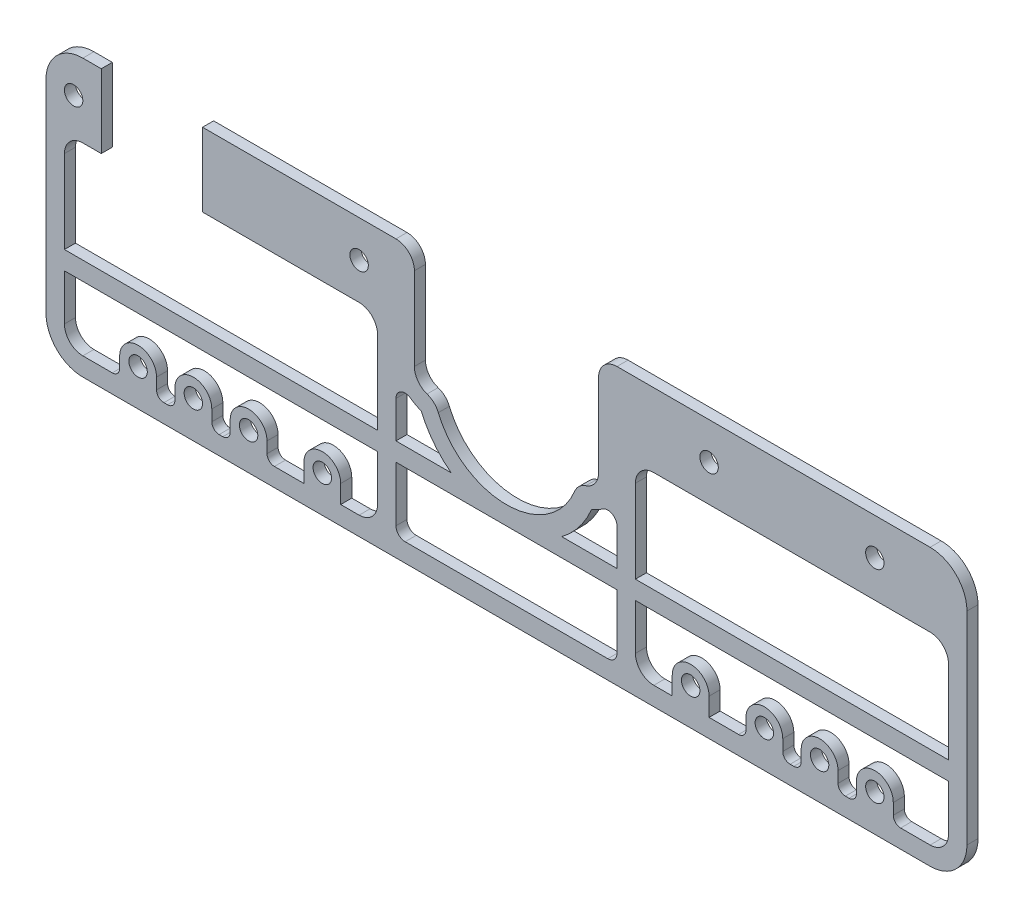
SolidWorks part; units mm, degrees
ref_plane "Front Plane" through (0, 0, 0) normal (0, 0, 1) x (1, 0, 0)
ref_plane "Top Plane" through (0, 0, 0) normal (0, 1, 0) x (1, 0, 0)
ref_plane "Right Plane" through (0, 0, 0) normal (1, 0, 0) x (0, 0, -1)
sketch "Sketch1" plane through (0, 0, 0) normal (0, 0, 1) x (1, 0, 0)
  line L0 (-40, 20) -> (-40, 55) construction
  line L4 (-250, -55) -> (-250, 3.1783)
  line L8 (-50, 75) -> (-230, 75) construction
  line L17 (0, -20) -> (0, -40)
  line L25 (0, -65) -> (0, -75)
  line L26 (0, 75) -> (0, -75) construction
  line L27 (-50, 95) -> (50, 95) construction
  line L34 (0, -75) -> (-230, -75)
  line L156 (-50, 75) -> (-230, 75) construction
  line L161 (0, -40) -> (0, -65)
  line L165 (-164.3309, 75) -> (-60, 75)
  line L167 (-230, 75) -> (-220, 75)
  line L171 (-250, 3.1783) -> (-250, 55)
  line L172 (-220, 75) -> (-164.3309, 75)
  line L173 (-50, 65) -> (-50, 20)
  arc A0 (-40, 20) -> (0, -20) centre (0, 20) ccw construction
  circle A1 centre (0, 20) radius 30 construction
  arc A4 (-230, -75) -> (-250, -55) centre (-230, -55) cw
  arc A5 (-250, 55) -> (-230, 75) centre (-230, 55) cw
  arc A124 (0, -20) -> (-37, 4.8013) centre (0, 20) cw
  arc A125 (-60, 75) -> (-50, 65) centre (-60, 65) cw
  arc A126 (-43.125, 10.5008) -> (-50, 20) centre (-40, 20) cw
  arc A127 (-37, 4.8013) -> (-43.125, 10.5008) centre (-46.25, 1.0016) ccw
  point P0 (0, 0)
  point P10 (-50, 10)
  point P11 (0, 50)
  point P30 (-40, 75)
  point P45 (0, -30)
  point P74 (0, 95)
  dimension "D3" = 80
  dimension "D4" = 60
  dimension "D6" = 55
  dimension "D7" = 75
  dimension "D10" = 10
  dimension "D11" = 20
  dimension "D8" = 10
  dimension "D5" = 10
  dimension "D9" = 20
  dimension "D13" = 210
  dimension "D16" = 100
  dimension "D17" = 20
  dimension "D26" = 250
extrude "Boss-Extrude1" add sketch "Sketch1" along normal blind 6
mirror "Mirror1" about plane through (0, -20, 6) normal (-1, 0, 0) of "Boss-Extrude1"
sketch "Sketch4" plane through (0, 0, 6) normal (0, 0, 1) x (1, 0, 0)
  line L0 (-230, -75) -> (230, -75) construction
  line L1 (-70, 25.101) -> (-70, -54.899)
  line L2 (-50, 20) -> (-50, 65) construction
  line L7 (-240, -55) -> (-240, 25.101)
  line L8 (-250, 55) -> (-250, -55) construction
  line L11 (-110, 35.101) -> (-80, 35.101)
  line L12 (-110, 35.101) -> (-140, 35.101)
  line L13 (-230, 35.101) -> (-140, 35.101)
  line L15 (-230, -65) -> (-210, -65)
  line L16 (-210, -65) -> (-210, -55)
  line L17 (-190, -55) -> (-190, -65)
  line L18 (-190, -65) -> (-110, -65)
  line L19 (-110, -65) -> (-110, -55)
  line L20 (-90, -55) -> (-90, -64.899)
  line L21 (-90, -64.899) -> (-80, -64.899)
  circle A1 centre (-200, -55) radius 5
  circle A2 centre (-100, -55) radius 5
  arc A6 (-230, -65) -> (-240, -55) centre (-230, -55) cw
  arc A12 (-210, -55) -> (-190, -55) centre (-200, -55) cw
  arc A13 (-110, -55) -> (-90, -55) centre (-100, -55) cw
  arc A14 (-240, 25.101) -> (-230, 35.101) centre (-230, 25.101) cw
  arc A15 (-70, -54.899) -> (-80, -64.899) centre (-80, -54.899) cw
  arc A16 (-70, 25.101) -> (-80, 35.101) centre (-80, 25.101) ccw
  point P0 (0, -75)
  dimension "D13" = 10
  dimension "D17" = 10
  dimension "D2" = 10
  dimension "D3" = 200
  dimension "D4" = 100
  dimension "D7" = 20
  dimension "D9" = 10
  dimension "D11" = 20
  dimension "D16" = 80
extrude "Cut-Extrude2" cut sketch "Sketch4" against normal through all contours L7 A6 L15 L16 | L13 | L17 L18 L19 | L20 L21 A15 L1 A16 L11 | A1 | A2 region at (-155.2296, -13.1384, 6) region at (-200, -55, 6) region at (-100, -55, 6)
mirror "Mirror2" about plane through (0, 0, 0) normal (1, 0, 0) of "Cut-Extrude2"
sketch "Sketch8" plane through (0, 0, 6) normal (0, 0, 1) x (1, 0, 0)
  line L0 (-60, 0) -> (-60, -64.899)
  line L2 (-60, -64.899) -> (60, -64.899)
  line L3 (60, -64.899) -> (60, 0)
  line L4 (-90, -64.899) -> (-80, -64.899) construction
  arc A0 (43.125, 10.5008) -> (50, 20) centre (40, 20) ccw construction
  arc A1 (43.125, 10.5008) -> (37, 4.8013) centre (46.25, 1.0016) ccw construction
  arc A2 (-37, 4.8013) -> (-43.125, 10.5008) centre (-46.25, 1.0016) ccw construction
  arc A3 (-50, 20) -> (-43.125, 10.5008) centre (-40, 20) ccw construction
  arc A4 (-37, 4.8013) -> (37, 4.8013) centre (0, 20) ccw construction
  arc A5 (43.125, 10.5008) -> (50, 20) centre (40, 20) ccw construction
  arc A6 (43.125, 10.5008) -> (37, 4.8013) centre (46.25, 1.0016) ccw construction
  arc A7 (-37, 4.8013) -> (-43.125, 10.5008) centre (-46.25, 1.0016) ccw construction
  arc A8 (-50, 20) -> (-43.125, 10.5008) centre (-40, 20) ccw construction
  arc A9 (-37, 4.8013) -> (37, 4.8013) centre (0, 20) ccw construction
  arc A10 (-52, 4) -> (-46.25, 1.0016) centre (-40, 20) ccw
  arc A11 (-46.25, 1.0016) -> (-46.25, 1.0016) centre (-46.25, 1.0016) ccw
  arc A12 (-46.25, 1.0016) -> (46.25, 1.0016) centre (0, 20) ccw
  arc A13 (46.25, 1.0016) -> (46.25, 1.0016) centre (46.25, 1.0016) ccw
  arc A14 (46.25, 1.0016) -> (52, 4) centre (40, 20) ccw
  arc A15 (46.25, 1.0016) -> (60, 20) centre (40, 20) ccw construction
  arc A16 (60, 0) -> (52, 4) centre (55, 0) ccw
  arc A17 (-60, 20) -> (-46.25, 1.0016) centre (-40, 20) ccw construction
  arc A18 (-60, 0) -> (-52, 4) centre (-55, 0) cw
  dimension "D2" = 5
  dimension "D1" = 10
extrude "Cut-Extrude5" cut sketch "Sketch8" against normal through all
fillet "Fillet5" radius 5 1 edges at (-60, -64.899, 3)
fillet "Fillet6" radius 5 1 edges at (60, -64.899, 3)
sketch "Sketch9" plane through (0, 0, 0) normal (0, 0, -1) x (-1, 0, 0)
  line L0 (-250, 55) -> (-250, -55) construction
  line L2 (250, 55) -> (250, -55) construction
  line L3 (165, 75) -> (165, 35.101)
  line L4 (60, 75) -> (230, 75) construction
  line L5 (230, 35.101) -> (80, 35.101) construction
  line L6 (165, 35.101) -> (220, 35.101)
  line L7 (220, 35.101) -> (220, 75)
  line L8 (220, 75) -> (165, 75)
  circle A0 centre (-200, 55) radius 5
  circle A1 centre (-110, 55) radius 5
  circle A2 centre (80, 55) radius 5
  circle A3 centre (235, 55) radius 5
  dimension "D1" = 10
  dimension "D3" = 90
  dimension "D4" = 15
  dimension "D5" = 170
  dimension "D7" = 20
  dimension "D2" = 50
  dimension "D6" = 55
  dimension "D8" = 30
extrude "Cut-Extrude6" cut sketch "Sketch9" against normal through all
sketch "Sketch10" plane through (0, 0, 0) normal (0, 0, -1) x (-1, 0, 0)
  line L0 (-250, -20) -> (250, -20)
  line L1 (-250, 55) -> (-250, -55) construction
  line L2 (250, 55) -> (250, -55) construction
  line L3 (250, -20) -> (250, -30)
  line L4 (250, -30) -> (-250, -30)
  line L5 (-250, -30) -> (-250, -20)
  arc A0 (-37, 4.8013) -> (37, 4.8013) centre (0, 20) ccw construction
  arc A1 (-46.25, 1.0016) -> (46.25, 1.0016) centre (0, 20) ccw construction
extrude "Boss-Extrude2" add sketch "Sketch10" against normal up to surface (6 mm away) up to face at (195, 55, 6)
sketch "Sketch11" plane through (0, 0, 0) normal (0, 0, -1) x (-1, 0, 0)
  line L0 (-190, -55) -> (-190, -65) construction
  line L1 (-210, -65) -> (-210, -55) construction
  line L4 (-190, -55) -> (-190, -61)
  line L5 (-210, -61) -> (-210, -55)
  line L6 (-186, -65) -> (-185, -65)
  line L7 (-190, -65) -> (-110, -65) construction
  line L8 (-214, -65) -> (-215, -65)
  line L9 (-230, -65) -> (-210, -65) construction
  line L10 (-160, -55) -> (-160, -61)
  line L11 (-180, -61) -> (-180, -55)
  line L12 (-156, -65) -> (-155, -65)
  line L13 (-184, -65) -> (-185, -65)
  line L14 (-130, -55) -> (-130, -61)
  line L15 (-150, -61) -> (-150, -55)
  line L16 (-126, -65) -> (-125, -65)
  line L17 (-154, -65) -> (-155, -65)
  line L18 (-215, -65) -> (-215, -66.4294)
  line L19 (-215, -66.4294) -> (-125, -66.4294)
  line L20 (-125, -66.4294) -> (-125, -65)
  circle A0 centre (-200, -55) radius 5 construction
  arc A1 (-190, -55) -> (-210, -55) centre (-200, -55) ccw construction
  circle A4 centre (-200, -55) radius 5
  arc A5 (-190, -55) -> (-210, -55) centre (-200, -55) ccw
  arc A6 (-186, -65) -> (-190, -61) centre (-186, -61) cw
  arc A7 (-210, -61) -> (-214, -65) centre (-214, -61) cw
  circle A8 centre (-170, -55) radius 5
  arc A9 (-160, -55) -> (-180, -55) centre (-170, -55) ccw
  arc A10 (-156, -65) -> (-160, -61) centre (-156, -61) cw
  arc A11 (-180, -61) -> (-184, -65) centre (-184, -61) cw
  circle A12 centre (-140, -55) radius 5
  arc A13 (-130, -55) -> (-150, -55) centre (-140, -55) ccw
  arc A14 (-126, -65) -> (-130, -61) centre (-126, -61) cw
  arc A15 (-150, -61) -> (-154, -65) centre (-154, -61) cw
  dimension "D3" = 4
  dimension "D1" = 5
  dimension "D2" = 5
  dimension "D4" = 3
extrude "Boss-Extrude3" add sketch "Sketch11" against normal up to surface (6 mm away) contours L15 A15 L17 L12 A10 L10 A9 L11 A11 L13 L6 A6 L4 A5 L5 A7 L8 L18 L19 L20 L16 A14 L14 A13 A4 A8 A12 region at (190.9252, -58, 0) up to face at (-50.2056, -6.7719, 6)
mirror "Mirror3" about plane through (0, 0, 0) normal (1, 0, 0) of "Boss-Extrude3"
